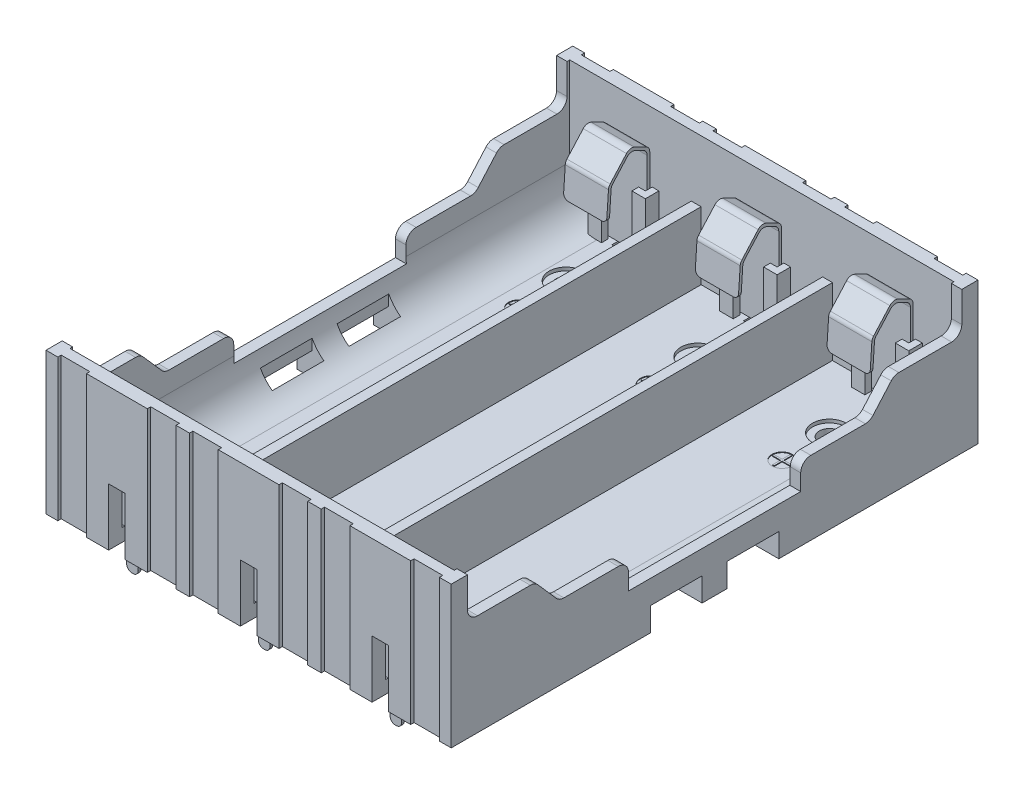
SolidWorks part; units mm, degrees
material "ABS"
ref_plane "Спереди" through (0, 0, 0) normal (0, 0, 1) x (1, 0, 0)
ref_plane "Сверху" through (0, 0, 0) normal (0, 1, 0) x (1, 0, 0)
ref_plane "Справа" through (0, 0, 0) normal (1, 0, 0) x (0, 0, -1)
other "Configuration Table"
sketch "Эскиз1" plane through (0, 0, 0) normal (0, 1, 0) x (1, 0, 0)
  line L1 (-30, 39) -> (30, 39)
  line L2 (-30, 39) -> (-30, -39)
  line L3 (-30, -39) -> (30, -39)
  line L4 (30, 39) -> (30, -39)
  line L5 (-30, 39) -> (30, -39) construction
  line L6 (-30, -39) -> (30, 39) construction
  point P0 (0, 0)
  dimension "D1" = 78
  dimension "D2" = 60
extrude "Основа" add sketch "Эскиз1" along normal blind 21
sketch "Эскиз2" plane through (0, 0, 0) normal (0, 1, 0) x (1, 0, 0)
  line L1 (30, 39) -> (-30, 39) construction
  line L2 (-4.5, 39) -> (-4.5, 38.5)
  line L3 (-4.5, 38.5) -> (-8.75, 38.5)
  line L4 (-8.75, 38.5) -> (-8.75, 39)
  line L5 (-8.75, 39) -> (-10.75, 39)
  line L6 (-10.75, 39) -> (-10.75, 38.5)
  line L7 (-10.75, 38.5) -> (-15, 38.5)
  line L8 (-15, 38.5) -> (-15, 39)
  line L9 (-15, 39) -> (-24, 39)
  line L10 (-24, 39) -> (-24, 38.5)
  line L11 (-24, 38.5) -> (-28.25, 38.5)
  line L12 (-28.25, 38.5) -> (-28.25, 39)
  line L13 (-28.25, 39) -> (-30, 39)
  line L14 (-30, 39) -> (-30, 49.7572)
  line L15 (-30, 49.7572) -> (30, 49.7572)
  line L16 (0, 49.7572) -> (0, 39)
  line L17 (4.5, 39) -> (-4.5, 39)
  line L18 (30, 39) -> (30, 49.7572)
  line L19 (15, 39) -> (24, 39)
  line L20 (24, 39) -> (24, 38.5)
  line L21 (28.25, 38.5) -> (28.25, 39)
  line L22 (24, 38.5) -> (28.25, 38.5)
  line L23 (28.25, 39) -> (30, 39)
  line L24 (15, 38.5) -> (15, 39)
  line L25 (10.75, 38.5) -> (15, 38.5)
  line L26 (10.75, 39) -> (10.75, 38.5)
  line L27 (8.75, 39) -> (10.75, 39)
  line L28 (4.5, 39) -> (4.5, 38.5)
  line L29 (4.5, 38.5) -> (8.75, 38.5)
  line L30 (8.75, 38.5) -> (8.75, 39)
  point P22 (0, 39)
  dimension "D1" = 9
  dimension "D2" = 2
  dimension "D3" = 4.25
  dimension "D4" = 0.5
extrude "Рёбра" cut sketch "Эскиз2" along normal through all contours L29 L30 L27 L26 L25 L24 L19 L20 L22 L21 L23 L18 L15 L16 L17 L28 | L17 L16 L15 L14 L13 L12 L11 L10 L9 L8 L7 L6 L5 L4 L3 L2 region at (-15.004, 0, -44.2695) region at (15.004, 0, -44.2695)
mirror "Зеркальное отражение1" about plane through (0, 0, 0) normal (0, 0, 1) of "Рёбра"
sketch "Эскиз3" plane through (0, 21, 0) normal (0, 1, 0) x (1, 0, 0)
  line L0 (19.45, 0) -> (-19.45, 0) construction
  line L1 (9, 37) -> (-9, 37)
  line L2 (9, 37) -> (9, -37)
  line L3 (9, -37) -> (-9, -37)
  line L4 (-9, 37) -> (-9, -37)
  line L5 (9, 37) -> (-9, -37) construction
  line L6 (9, -37) -> (-9, 37) construction
  line L8 (-28.45, 37) -> (-10.45, 37)
  line L9 (-28.45, 37) -> (-28.45, -37)
  line L10 (-28.45, -37) -> (-10.45, -37)
  line L11 (-10.45, 37) -> (-10.45, -37)
  line L12 (-28.45, 37) -> (-10.45, -37) construction
  line L13 (-28.45, -37) -> (-10.45, 37) construction
  line L15 (28.45, 37) -> (10.45, 37)
  line L16 (28.45, 37) -> (28.45, -37)
  line L17 (28.45, -37) -> (10.45, -37)
  line L18 (10.45, 37) -> (10.45, -37)
  line L19 (28.45, 37) -> (10.45, -37) construction
  line L20 (28.45, -37) -> (10.45, 37) construction
  point P0 (0, 0)
  point P9 (0, 0)
  dimension "D1" = 18
  dimension "D2" = 74
  dimension "D3" = 1.45
extrude "Отсеки" cut sketch "Эскиз3" against normal blind 19.1
fillet "Скругление1" radius 6 2 edges at (28.45, 1.9, 0) (-28.45, 1.9, 0)
sketch "Эскиз4" plane through (0, 0, 0) normal (1, 0, 0) x (0, 0, -1)
  line L0 (37, 21) -> (-37, 21) construction
  line L1 (37, 30.1) -> (-37, 30.1)
  line L2 (37, 30.1) -> (37, 11.9)
  line L3 (37, 11.9) -> (-37, 11.9)
  line L4 (-37, 30.1) -> (-37, 11.9)
  line L5 (37, 30.1) -> (-37, 11.9) construction
  line L6 (37, 11.9) -> (-37, 30.1) construction
  line L7 (-37, 1.9) -> (-37, 21) construction
  line L8 (37, 1.9) -> (-37, 1.9) construction
  point P0 (0, 21)
  dimension "D1" = 10
extrude "Уменьшение внутренних стенок" cut sketch "Эскиз4" against normal blind 15 and the other way blind 15
sketch "Эскиз5" plane through (30, 0, 0) normal (1, 0, 0) x (0, 0, -1)
  line L0 (-39, 21) -> (-36.6, 21)
  line L1 (-39, 21) -> (39, 21) construction
  line L2 (-36.6, 21) -> (-36.6, 15)
  line L3 (-36.6, 15) -> (-26.6, 15)
  line L4 (-26.6, 15) -> (-23, 10.9)
  line L5 (-23, 10.9) -> (-12.75, 10.9)
  line L6 (-12.75, 10.9) -> (-12.75, 7)
  line L7 (-12.75, 7) -> (12.75, 7)
  line L8 (0, 7) -> (0, 0) construction
  line L9 (-36.6, 21) -> (36.6, 21)
  line L10 (12.75, 10.9) -> (12.75, 7)
  line L11 (23, 10.9) -> (12.75, 10.9)
  line L12 (26.6, 15) -> (23, 10.9)
  line L13 (36.6, 15) -> (26.6, 15)
  line L14 (36.6, 21) -> (36.6, 15)
  point P20 (0, 21)
  line M12 (39, 21) -> (-39, 21)
  dimension "D1" = 12.75
  dimension "D2" = 10.25
  dimension "D3" = 2.4
  dimension "D4" = 10
  dimension "D5" = 6
  dimension "D6" = 3.9
  dimension "D7" = 7
extrude "Уменьшение внешних стенок" cut sketch "Эскиз5" against normal blind 15 contours L14 L2 L3 L4 L5 L6 L7 L10 L11 L12 L13 M12 region at (30, 15.4166, 0)
fillet "Скругление2" radius 1.5 8 edges at (29.225, 15, -36.6) (29.225, 15, -26.6) (29.225, 10.9, -23) (29.225, 10.9, -12.75) (29.225, 10.9, 12.75) (29.225, 10.9, 23) (29.225, 15, 26.6) (29.225, 15, 36.6)
mirror "Зеркальное отражение2" about plane through (0, 0, 0) normal (1, 0, 0) of "Скругление2", "Уменьшение внешних стенок"
sketch "Эскиз6" plane through (0, 0, 0) normal (0, 1, 0) x (1, 0, 0)
  line L0 (-4.5, -39) -> (4.5, -39) construction
  line L1 (-1.225, -42.5) -> (1.225, -42.5)
  line L2 (-1.225, -42.5) -> (-1.225, -35.5)
  line L3 (-1.225, -35.5) -> (1.225, -35.5)
  line L4 (1.225, -42.5) -> (1.225, -35.5)
  line L5 (-1.225, -42.5) -> (1.225, -35.5) construction
  line L6 (-1.225, -35.5) -> (1.225, -42.5) construction
  line L7 (-30, 0) -> (30, 0) construction
  line L8 (30, -39) -> (30, 39) construction
  line L9 (-24, -39) -> (-15, -39) construction
  line L10 (-20.725, -42.5) -> (-18.275, -42.5)
  line L11 (-20.725, -42.5) -> (-20.725, -35.5)
  line L12 (-20.725, -35.5) -> (-18.275, -35.5)
  line L13 (-18.275, -42.5) -> (-18.275, -35.5)
  line L14 (-20.725, -42.5) -> (-18.275, -35.5) construction
  line L15 (-20.725, -35.5) -> (-18.275, -42.5) construction
  line L16 (15, -39) -> (24, -39) construction
  line L17 (20.725, -42.5) -> (18.275, -42.5)
  line L18 (20.725, -42.5) -> (20.725, -35.5)
  line L19 (20.725, -35.5) -> (18.275, -35.5)
  line L20 (18.275, -42.5) -> (18.275, -35.5)
  line L21 (20.725, -42.5) -> (18.275, -35.5) construction
  line L22 (20.725, -35.5) -> (18.275, -42.5) construction
  line L23 (20.725, 35.5) -> (18.275, 42.5) construction
  line L24 (20.725, 42.5) -> (18.275, 35.5) construction
  line L25 (-20.725, 35.5) -> (-18.275, 42.5) construction
  line L26 (-20.725, 42.5) -> (-18.275, 35.5) construction
  line L27 (-1.225, 35.5) -> (1.225, 42.5) construction
  line L28 (-1.225, 42.5) -> (1.225, 35.5) construction
  line L29 (18.275, 42.5) -> (18.275, 35.5)
  line L30 (20.725, 35.5) -> (18.275, 35.5)
  line L31 (20.725, 42.5) -> (20.725, 35.5)
  line L32 (20.725, 42.5) -> (18.275, 42.5)
  line L33 (-18.275, 42.5) -> (-18.275, 35.5)
  line L34 (-20.725, 35.5) -> (-18.275, 35.5)
  line L35 (-20.725, 42.5) -> (-20.725, 35.5)
  line L36 (-20.725, 42.5) -> (-18.275, 42.5)
  line L37 (1.225, 42.5) -> (1.225, 35.5)
  line L38 (-1.225, 35.5) -> (1.225, 35.5)
  line L39 (-1.225, 42.5) -> (-1.225, 35.5)
  line L40 (-1.225, 42.5) -> (1.225, 42.5)
  point P0 (0, -39)
  point P7 (-19.5, -39)
  point P13 (0, 0)
  point P21 (19.5, -39)
  point P40 (19.5, 39)
  point P41 (-19.5, 39)
  point P42 (0, 39)
  dimension "D1" = 2.45
  dimension "D2" = 3.5
extrude "Вырезы под контакты" cut sketch "Эскиз6" along normal blind 8.5
sketch "Эскиз7" plane through (0, 0, 0) normal (0, 1, 0) x (1, 0, 0)
  line L0 (0, -35.5) -> (0, 35.5) construction
  line L1 (1.225, -35.5) -> (-1.225, -35.5) construction
  line L2 (-1.225, 35.5) -> (1.225, 35.5) construction
  line L3 (0, 0) -> (-26.025, 0) construction
  line L4 (-26.025, -23.825) -> (-26.025, 23.825) construction
  line L5 (-24, -38.5) -> (-28.25, -38.5) construction
  line L6 (-24.325, -10.8) -> (-27.725, -10.8)
  line L7 (-24.325, -10.8) -> (-24.325, -36.85)
  line L8 (-24.325, -36.85) -> (-27.725, -36.85)
  line L9 (-27.725, -10.8) -> (-27.725, -36.85)
  line L10 (-24.325, -10.8) -> (-27.725, -36.85) construction
  line L11 (-24.325, -36.85) -> (-27.725, -10.8) construction
  line L12 (-24.325, 10.8) -> (-27.725, 10.8)
  line L13 (-24.325, 10.8) -> (-24.325, 36.85)
  line L14 (-24.325, 36.85) -> (-27.725, 36.85)
  line L15 (-27.725, 10.8) -> (-27.725, 36.85)
  line L16 (-24.325, 10.8) -> (-27.725, 36.85) construction
  line L17 (-24.325, 36.85) -> (-27.725, 10.8) construction
  line L18 (-27.725, -1.375) -> (-24.325, -1.375)
  line L19 (-27.725, -1.375) -> (-27.725, 1.375)
  line L20 (-27.725, 1.375) -> (-24.325, 1.375)
  line L21 (-24.325, -1.375) -> (-24.325, 1.375)
  line L22 (-27.725, -1.375) -> (-24.325, 1.375) construction
  line L23 (-27.725, 1.375) -> (-24.325, -1.375) construction
  line L24 (24.325, 36.85) -> (27.725, 36.85)
  line L25 (24.325, 10.8) -> (24.325, 36.85)
  line L26 (27.725, 10.8) -> (27.725, 36.85)
  line L27 (24.325, 10.8) -> (27.725, 10.8)
  line L28 (24.325, -10.8) -> (27.725, -10.8)
  line L29 (24.325, -10.8) -> (24.325, -36.85)
  line L30 (27.725, -10.8) -> (27.725, -36.85)
  line L31 (24.325, -36.85) -> (27.725, -36.85)
  line L32 (27.725, -1.375) -> (27.725, 1.375)
  line L33 (27.725, -1.375) -> (24.325, -1.375)
  line L34 (24.325, -1.375) -> (24.325, 1.375)
  line L35 (27.725, 1.375) -> (24.325, 1.375)
  point P11 (-26.025, 0)
  dimension "D1" = 21.6
  dimension "D2" = 3.4
  dimension "D3" = 2.75
  dimension "D4" = 24.325
  dimension "D5" = 1.65
extrude "Пазы снизу" cut sketch "Эскиз7" along normal blind 1
sketch "Эскиз8" plane through (0, 0, 0) normal (0, 0, 1) x (1, 0, 0)
  line L0 (24.325, 1) -> (27.725, 1)
  line L1 (27.725, 1) -> (27.725, 3.073)
  arc A0 (24.325, 1) -> (27.725, 3.073) centre (22.45, 7.9) ccw
  arc A1 (22.45, 1.9) -> (28.45, 7.9) centre (22.45, 7.9) ccw construction
  arc A2 (22.45, 1.9) -> (28.45, 7.9) centre (22.45, 7.9) ccw construction
extrude "Вырез-Вытянуть9" cut sketch "Эскиз8" against normal up to surface and the other way up to surface up to face at (26.025, 0.5, -1.375) other way up to face at (26.025, 0.5, 1.375)
extrude "Вырез-Вытянуть10" cut sketch "Эскиз8<3>" along direction (0, 0, 1) on the side against the normal up to surface (36.85 mm away) from surface contours A0 L0 L1 region at (26.7298, 1.6233, 0) up to face at (26.025, 0.5, -36.85) starting at face at (26.025, 0.5, -10.8)
sketch "Эскиз8<3>" plane through (0, 0, 0) normal (0, 0, 1) x (1, 0, 0) same geometry as "Эскиз8"
extrude "Вырез-Вытянуть11" cut sketch "Эскиз8<4>" along normal up to surface (36.85 mm away) from surface up to face at (26.025, 0.5, 36.85) starting at face at (26.025, 0.5, 10.8)
sketch "Эскиз8<4>" plane through (0, 0, 0) normal (0, 0, 1) x (1, 0, 0) same geometry as "Эскиз8"
mirror "Зеркальное отражение3" about plane through (0, 0, 0) normal (1, 0, 0) of "Вырез-Вытянуть11", "Вырез-Вытянуть10", "Вырез-Вытянуть9"
sketch "Эскиз9" plane through (0, 0, 0) normal (0, 1, 0) x (1, 0, 0)
  line L0 (-30, 39) -> (-30, -39) construction
  line L1 (-34, -9.5) -> (-26, -9.5)
  line L2 (-34, -9.5) -> (-34, -1.85)
  line L3 (-34, -1.85) -> (-26, -1.85)
  line L4 (-26, -9.5) -> (-26, -1.85)
  line L5 (-34, -9.5) -> (-26, -1.85) construction
  line L6 (-34, -1.85) -> (-26, -9.5) construction
  line L7 (0, 0) -> (-30, 0) construction
  line L8 (-34, 1.85) -> (-26, 1.85)
  line L9 (-34, 1.85) -> (-34, 9.5)
  line L10 (-34, 9.5) -> (-26, 9.5)
  line L11 (-26, 1.85) -> (-26, 9.5)
  line L12 (-34, 1.85) -> (-26, 9.5) construction
  line L13 (-34, 9.5) -> (-26, 1.85) construction
  line L14 (-30, 0) -> (-30, 5.675) construction
  line L15 (-30, 0) -> (-30, -5.675) construction
  line L16 (0, 0) -> (0, -8.7492) construction
  line L17 (30, 0) -> (30, -5.675) construction
  line L18 (30, 0) -> (30, 5.675) construction
  line L19 (34, 9.5) -> (26, 1.85) construction
  line L20 (34, 1.85) -> (26, 9.5) construction
  line L21 (34, -1.85) -> (26, -9.5) construction
  line L22 (34, -9.5) -> (26, -1.85) construction
  line L23 (26, 1.85) -> (26, 9.5)
  line L24 (34, 9.5) -> (26, 9.5)
  line L25 (34, 1.85) -> (34, 9.5)
  line L26 (34, 1.85) -> (26, 1.85)
  line L27 (26, -9.5) -> (26, -1.85)
  line L28 (34, -1.85) -> (26, -1.85)
  line L29 (34, -9.5) -> (34, -1.85)
  line L30 (34, -9.5) -> (26, -9.5)
  point P0 (-30, -5.675)
  point P7 (-30, 5.675)
  point P29 (30, 5.675)
  point P30 (30, -5.675)
  dimension "D1" = 7.65
  dimension "D2" = 4
  dimension "D3" = 3.7
extrude "Пазы сбоку" cut sketch "Эскиз9" along normal blind 3.5
sketch "Эскиз10" plane through (0, 0, 0) normal (0, 1, 0) x (1, 0, 0)
  line L2 (-26, -9.5) -> (-26, -1.85) construction
  line L3 (-26, 1.85) -> (-26, 9.5) construction
  line L4 (0, 0) -> (0, -13.336) construction
  line L5 (27.75, 1.85) -> (26, 1.85)
  line L6 (-26, -9.5) -> (-26, -1.85)
  line L7 (-26, 1.85) -> (-26, 9.5)
  line L8 (-26, -1.85) -> (-27.75, -1.85)
  line L9 (-26, -1.85) -> (-30, -1.85) construction
  line L10 (-27.75, -1.85) -> (-27.75, -9.5)
  line L11 (-30, -9.5) -> (-26, -9.5) construction
  line L12 (-27.75, -9.5) -> (-26, -9.5)
  line L13 (-26, 9.5) -> (-27.75, 9.5)
  line L14 (-26.5292, 9.5) -> (-30, 9.5) construction
  line L15 (-27.75, 9.5) -> (-27.75, 1.85)
  line L16 (-30, 1.85) -> (-26, 1.85) construction
  line L17 (-27.75, 1.85) -> (-26, 1.85)
  line L18 (27.75, 9.5) -> (27.75, 1.85)
  line L19 (26, 9.5) -> (27.75, 9.5)
  line L20 (27.75, -9.5) -> (26, -9.5)
  line L21 (27.75, -1.85) -> (27.75, -9.5)
  line L22 (26, -1.85) -> (27.75, -1.85)
  line L23 (26, 1.85) -> (26, 9.5)
  line L24 (26, -9.5) -> (26, -1.85)
  dimension "D1" = 1.75
extrude "Вырез-Вытянуть15" cut sketch "Эскиз10" along normal through all
sketch "Эскиз11" plane through (0, 0, 0) normal (0, 1, 0) x (1, 0, 0)
  line L0 (-19.5, 35.5) -> (-19.5, 27.5) construction
  line L1 (19.5, -27.5) -> (-19.5, -27.5) construction
  line L2 (19.5, -27.5) -> (19.5, 27.5) construction
  line L3 (19.5, 27.5) -> (-19.5, 27.5) construction
  line L4 (-19.5, -27.5) -> (-19.5, 27.5) construction
  line L5 (19.5, -27.5) -> (-19.5, 27.5) construction
  line L6 (19.5, 27.5) -> (-19.5, -27.5) construction
  line L7 (-18.275, 35.5) -> (-20.725, 35.5) construction
  circle A0 centre (-19.5, 27.5) radius 1.5
  circle A1 centre (0, 27.5) radius 1.5
  circle A2 centre (19.5, 27.5) radius 1.5
  circle A3 centre (19.5, -27.5) radius 1.5
  circle A4 centre (0, -27.5) radius 1.5
  circle A5 centre (-19.5, -27.5) radius 1.5
  point P0 (0, 0)
  dimension "D2" = 3
  dimension "D1" = 55
extrude "Крепежные отверстия" cut sketch "Эскиз11" along normal through all
sketch "Эскиз12" plane through (0, 0, 0) normal (0, 1, 0) x (1, 0, 0)
  circle A0 centre (-19.5, 27.5) radius 1.5 construction
  circle A1 centre (0, 27.5) radius 1.5 construction
  circle A2 centre (19.5, 27.5) radius 1.5 construction
  circle A3 centre (19.5, -27.5) radius 1.5 construction
  circle A4 centre (0, -27.5) radius 1.5 construction
  circle A5 centre (-19.5, -27.5) radius 1.5 construction
  circle A6 centre (-19.5, 27.5) radius 1.5
  circle A7 centre (0, 27.5) radius 1.5
  circle A8 centre (19.5, 27.5) radius 1.5
  circle A9 centre (19.5, -27.5) radius 1.5
  circle A10 centre (0, -27.5) radius 1.5
  circle A11 centre (-19.5, -27.5) radius 1.5
  circle A12 centre (-19.5, 27.5) radius 2.8
  circle A13 centre (0, 27.5) radius 2.8
  circle A14 centre (19.5, 27.5) radius 2.8
  circle A15 centre (19.5, -27.5) radius 2.8
  circle A16 centre (0, -27.5) radius 2.8
  circle A17 centre (-19.5, -27.5) radius 2.8
  dimension "D1" = 1.3
extrude "Юбки отверстий" add sketch "Эскиз12" against normal blind 0.3
sketch "Эскиз13" plane through (0, 1.9, 0) normal (0, 1, 0) x (1, 0, 0)
  circle A0 centre (-19.5, -27.5) radius 1.5 construction
  circle A1 centre (0, -27.5) radius 1.5 construction
  circle A2 centre (19.5, 27.5) radius 1.5 construction
  circle A3 centre (0, 27.5) radius 1.5 construction
  circle A4 centre (-19.5, 27.5) radius 1.5 construction
  circle A5 centre (-19.5, -27.5) radius 1.5
  circle A6 centre (0, -27.5) radius 1.5
  circle A7 centre (19.5, 27.5) radius 1.5
  circle A8 centre (0, 27.5) radius 1.5
  circle A9 centre (-19.5, 27.5) radius 1.5
  circle A10 centre (19.5, -27.5) radius 1.5 construction
  circle A11 centre (19.5, -27.5) radius 1.5
  circle A12 centre (-19.5, -27.5) radius 2.5
  circle A13 centre (0, -27.5) radius 2.5
  circle A14 centre (19.5, 27.5) radius 2.5
  circle A15 centre (0, 27.5) radius 2.5
  circle A16 centre (-19.5, 27.5) radius 2.5
  circle A17 centre (19.5, -27.5) radius 2.5
  dimension "D1" = 1
extrude "Вырез-Вытянуть17" cut sketch "Эскиз13" against normal blind 0.5
sketch "Эскиз14" plane through (0, 1.9, 0) normal (0, 1, 0) x (1, 0, 0)
  line L0 (-19.5, 20.5) -> (-19.5, 27.5) construction
  line L1 (19.5, -20.5) -> (-19.5, -20.5) construction
  line L2 (19.5, -20.5) -> (19.5, 20.5) construction
  line L3 (19.5, 20.5) -> (-19.5, 20.5) construction
  line L4 (-19.5, -20.5) -> (-19.5, 20.5) construction
  line L5 (19.5, -20.5) -> (-19.5, 20.5) construction
  line L6 (19.5, 20.5) -> (-19.5, -20.5) construction
  line L7 (0.125, -19.2) -> (-0.125, -19.2)
  line L8 (-19.375, -19.2) -> (-19.625, -19.2)
  line L9 (-19.375, -19.2) -> (-19.375, -21.8)
  line L10 (-19.375, -21.8) -> (-19.625, -21.8)
  line L11 (-19.625, -19.2) -> (-19.625, -21.8)
  line L12 (-19.375, -19.2) -> (-19.625, -21.8) construction
  line L13 (-19.375, -21.8) -> (-19.625, -19.2) construction
  line L14 (-19.375, 21.8) -> (-19.625, 21.8)
  line L15 (-19.375, 21.8) -> (-19.375, 19.2)
  line L16 (-19.375, 19.2) -> (-19.625, 19.2)
  line L17 (-19.625, 21.8) -> (-19.625, 19.2)
  line L18 (-19.375, 21.8) -> (-19.625, 19.2) construction
  line L19 (-19.375, 19.2) -> (-19.625, 21.8) construction
  line L20 (-18.2, 20.625) -> (-20.8, 20.625)
  line L21 (-18.2, 20.625) -> (-18.2, 20.375)
  line L22 (-18.2, 20.375) -> (-20.8, 20.375)
  line L23 (-20.8, 20.625) -> (-20.8, 20.375)
  line L24 (-18.2, 20.625) -> (-20.8, 20.375) construction
  line L25 (-18.2, 20.375) -> (-20.8, 20.625) construction
  line L26 (0.125, -19.2) -> (0.125, -21.8)
  line L27 (0.125, -21.8) -> (-0.125, -21.8)
  line L28 (-0.125, -19.2) -> (-0.125, -21.8)
  line L29 (0.125, 21.8) -> (-0.125, 21.8)
  line L30 (0.125, 21.8) -> (0.125, 19.2)
  line L31 (0.125, 19.2) -> (-0.125, 19.2)
  line L32 (-0.125, 21.8) -> (-0.125, 19.2)
  line L33 (1.3, 20.625) -> (-1.3, 20.625)
  line L34 (1.3, 20.625) -> (1.3, 20.375)
  line L35 (1.3, 20.375) -> (-1.3, 20.375)
  line L36 (-1.3, 20.625) -> (-1.3, 20.375)
  line L37 (0, -20.5) -> (0, 20.5) construction
  line L38 (0.125, -19.2) -> (-0.125, -21.8) construction
  line L39 (0.125, -21.8) -> (-0.125, -19.2) construction
  line L40 (0.125, 21.8) -> (-0.125, 19.2) construction
  line L41 (0.125, 19.2) -> (-0.125, 21.8) construction
  line L42 (1.3, 20.625) -> (-1.3, 20.375) construction
  line L43 (1.3, 20.375) -> (-1.3, 20.625) construction
  line L44 (19.625, -19.2) -> (19.375, -19.2)
  line L45 (19.625, -19.2) -> (19.625, -21.8)
  line L46 (19.625, -21.8) -> (19.375, -21.8)
  line L47 (19.375, -19.2) -> (19.375, -21.8)
  line L48 (19.625, 21.8) -> (19.375, 21.8)
  line L49 (19.625, 21.8) -> (19.625, 19.2)
  line L50 (19.625, 19.2) -> (19.375, 19.2)
  line L51 (19.375, 21.8) -> (19.375, 19.2)
  line L52 (20.8, 20.625) -> (18.2, 20.625)
  line L53 (20.8, 20.625) -> (20.8, 20.375)
  line L54 (20.8, 20.375) -> (18.2, 20.375)
  line L55 (18.2, 20.625) -> (18.2, 20.375)
  line L56 (19.5, -20.5) -> (19.5, 20.5) construction
  line L57 (19.625, -19.2) -> (19.375, -21.8) construction
  line L58 (19.625, -21.8) -> (19.375, -19.2) construction
  line L59 (19.625, 21.8) -> (19.375, 19.2) construction
  line L60 (19.625, 19.2) -> (19.375, 21.8) construction
  line L61 (20.8, 20.625) -> (18.2, 20.375) construction
  line L62 (20.8, 20.375) -> (18.2, 20.625) construction
  circle A0 centre (-19.5, 20.5) radius 1.5
  circle A1 centre (-19.5, -20.5) radius 1.5
  circle A2 centre (0, 20.5) radius 1.5
  circle A3 centre (0, -20.5) radius 1.5
  circle A4 centre (19.5, 20.5) radius 1.5
  circle A5 centre (19.5, -20.5) radius 1.5
  point P0 (0, 0)
  dimension "D2" = 3
  dimension "D1" = 7
  dimension "D3" = 2.6
  dimension "D4" = 0.25
  dimension "D5" = 3
extrude "Полярность" cut sketch "Эскиз14" against normal blind 0.1 contours A3 L28 L7 L26 L27 | A5 L47 L44 L45 L46 | A1 L11 L8 L9 L10 | A0 L23 L20 L17 L14 L15 L21 L22 L16 | A2 L36 L33 L32 L29 L30 L34 L35 L31 | A4 L55 L52 L51 L48 L49 L53 L54 L50 region at (-20.9576, 1.9, -20.5) region at (-20.9576, 1.9, 20.5) region at (-1.4576, 1.9, -20.5) region at (-1.4576, 1.9, 20.5) region at (18.0424, 1.9, -20.5) region at (18.0424, 1.9, 20.5)
sketch "Эскиз15" plane through (0, 1.9, 0) normal (0, 1, 0) x (1, 0, 0)
  line L0 (-19.5, 35.5) -> (-19.5, 35) construction
  line L1 (-18.275, 35.5) -> (-20.725, 35.5) construction
  line L2 (-21.75, 35) -> (-17.25, 35) construction
  line L3 (-21.75, 35) -> (-23.75, 35)
  line L4 (-23.75, 35) -> (-23.75, 37)
  line L5 (28.45, 37) -> (-28.45, 37) construction
  line L6 (-23.75, 37) -> (-22.75, 37)
  line L7 (-22.75, 37) -> (-22.75, 36)
  line L8 (-22.75, 36) -> (-21.75, 36)
  line L9 (-21.75, 36) -> (-21.75, 35)
  line L10 (-17.25, 35) -> (-17.25, 36)
  line L11 (-17.25, 36) -> (-16.25, 36)
  line L12 (-16.25, 36) -> (-16.25, 37)
  line L13 (-16.25, 37) -> (-15.25, 37)
  line L14 (-15.25, 37) -> (-15.25, 35)
  line L15 (-15.25, 35) -> (-17.25, 35)
  line L16 (-2.25, 35) -> (-4.25, 35)
  line L17 (-4.25, 35) -> (-4.25, 37)
  line L18 (-4.25, 37) -> (-3.25, 37)
  line L19 (-3.25, 37) -> (-3.25, 36)
  line L20 (-3.25, 36) -> (-2.25, 36)
  line L21 (-2.25, 36) -> (-2.25, 35)
  line L22 (2.25, 35) -> (2.25, 36)
  line L23 (2.25, 36) -> (3.25, 36)
  line L24 (3.25, 36) -> (3.25, 37)
  line L25 (3.25, 37) -> (4.25, 37)
  line L26 (4.25, 37) -> (4.25, 35)
  line L27 (4.25, 35) -> (2.25, 35)
  line L28 (0, 35.5) -> (0, 35) construction
  line L29 (-2.25, 35) -> (2.25, 35) construction
  line L30 (17.25, 35) -> (15.25, 35)
  line L31 (15.25, 35) -> (15.25, 37)
  line L32 (15.25, 37) -> (16.25, 37)
  line L33 (16.25, 37) -> (16.25, 36)
  line L34 (16.25, 36) -> (17.25, 36)
  line L35 (17.25, 36) -> (17.25, 35)
  line L36 (21.75, 35) -> (21.75, 36)
  line L37 (21.75, 36) -> (22.75, 36)
  line L38 (22.75, 36) -> (22.75, 37)
  line L39 (22.75, 37) -> (23.75, 37)
  line L40 (23.75, 37) -> (23.75, 35)
  line L41 (23.75, 35) -> (21.75, 35)
  line L42 (19.5, 35.5) -> (19.5, 35) construction
  line L43 (17.25, 35) -> (21.75, 35) construction
  line L44 (30, 0) -> (-30, 0) construction
  line L45 (-30, -12.75) -> (-30, 12.75) construction
  line L46 (17.25, -35) -> (21.75, -35) construction
  line L47 (19.5, -35.5) -> (19.5, -35) construction
  line L48 (-2.25, -35) -> (2.25, -35) construction
  line L49 (0, -35.5) -> (0, -35) construction
  line L50 (-21.75, -35) -> (-17.25, -35) construction
  line L51 (-19.5, -35.5) -> (-19.5, -35) construction
  line L52 (23.75, -35) -> (21.75, -35)
  line L53 (23.75, -37) -> (23.75, -35)
  line L54 (22.75, -37) -> (23.75, -37)
  line L55 (22.75, -36) -> (22.75, -37)
  line L56 (21.75, -36) -> (22.75, -36)
  line L57 (21.75, -35) -> (21.75, -36)
  line L58 (17.25, -36) -> (17.25, -35)
  line L59 (16.25, -36) -> (17.25, -36)
  line L60 (16.25, -37) -> (16.25, -36)
  line L61 (15.25, -37) -> (16.25, -37)
  line L62 (15.25, -35) -> (15.25, -37)
  line L63 (17.25, -35) -> (15.25, -35)
  line L64 (4.25, -35) -> (2.25, -35)
  line L65 (4.25, -37) -> (4.25, -35)
  line L66 (3.25, -37) -> (4.25, -37)
  line L67 (3.25, -36) -> (3.25, -37)
  line L68 (2.25, -36) -> (3.25, -36)
  line L69 (2.25, -35) -> (2.25, -36)
  line L70 (-2.25, -36) -> (-2.25, -35)
  line L71 (-3.25, -36) -> (-2.25, -36)
  line L72 (-3.25, -37) -> (-3.25, -36)
  line L73 (-4.25, -37) -> (-3.25, -37)
  line L74 (-4.25, -35) -> (-4.25, -37)
  line L75 (-2.25, -35) -> (-4.25, -35)
  line L76 (-15.25, -35) -> (-17.25, -35)
  line L77 (-15.25, -37) -> (-15.25, -35)
  line L78 (-16.25, -37) -> (-15.25, -37)
  line L79 (-16.25, -36) -> (-16.25, -37)
  line L80 (-17.25, -36) -> (-16.25, -36)
  line L81 (-17.25, -35) -> (-17.25, -36)
  line L82 (-21.75, -36) -> (-21.75, -35)
  line L83 (-22.75, -36) -> (-21.75, -36)
  line L84 (-22.75, -37) -> (-22.75, -36)
  line L85 (-23.75, -37) -> (-22.75, -37)
  line L86 (-23.75, -35) -> (-23.75, -37)
  line L87 (-21.75, -35) -> (-23.75, -35)
  point P7 (-19.5, 35)
  point P24 (0, 35)
  point P39 (19.5, 35)
  point P55 (0, 0)
  point P98 (19.5, -35)
  point P99 (0, -35)
  point P100 (-19.5, -35)
  dimension "D1" = 2
  dimension "D2" = 1
  dimension "D3" = 8.5
  dimension "D4" = 2
  dimension "D5" = 3
extrude "Пазы для контактов" add sketch "Эскиз15" along normal blind 8.9
ref_plane "Для эскиза контактов" through (-19.5, 0, 0) normal (-1, 0, 0) x (0, 0, 1)
sketch "Эскиз16" plane through (-19.5, 0, 0) normal (-1, 0, 0) x (0, 0, 1)
  line L0 (-37, 6.35) -> (-36, 6.35) construction
  line L1 (-37, 10.8) -> (-37, 1.9) construction
  line L2 (-36, 10.8) -> (-36, 1.9) construction
  line L3 (-36.5, 17.26) -> (-36.5, 15.9523) construction
  line L4 (-36.5, 15.9523) -> (-33.8, 17.26)
  line L5 (-33.8, 17.26) -> (-30.8, 13.9059)
  line L6 (-30.8, 13.9059) -> (-30.5, 9.4159)
  line L7 (-36.5, 17.26) -> (-33.8, 17.26) construction
  line L8 (-36.5, 15.9523) -> (-36.5, 2)
  line L9 (-35.5, 0) -> (-39, 0) construction
  line L10 (-36.5, 2) -> (-36.5, -3.54) construction
  line L11 (-37, 1.9) -> (-35.5, 1.9) construction
  point P8 (-36.4926, -3.4204)
  point P12 (-36.4066, 16.649)
  point P14 (-36.6083, 15.954)
  point P17 (-36.5, 6.35)
  point P20 (-36.214, 3.8899)
  dimension "D1" = 20.8
  dimension "D2" = 3
  dimension "D3" = 4.5
  dimension "D4" = 6
  dimension "D5" = 5.7
  dimension "D6" = 2.7
  dimension "D7" = 3.54
  dimension "D8" = 0.1
extrude "Контакт" add sketch "Эскиз16" along normal mid plane 6.4 thin thin type mid plane wall 0.4
sketch "Эскиз17" plane through (0, 2, 0) normal (0, -1, 0) x (1, 0, 0)
  line L0 (-19.5, -36.7) -> (-19.5, -36.3) construction
  line L1 (-22.7, -36.7) -> (-16.3, -36.7) construction
  line L2 (-22.7, -36.3) -> (-16.3, -36.3) construction
  line L4 (-18.65, -36.3) -> (-20.35, -36.3)
  line L5 (-18.65, -36.3) -> (-18.65, -36.7)
  line L6 (-18.65, -36.7) -> (-20.35, -36.7)
  line L7 (-20.35, -36.3) -> (-20.35, -36.7)
  line L8 (-18.65, -36.3) -> (-20.35, -36.7) construction
  line L9 (-18.65, -36.7) -> (-20.35, -36.3) construction
  point P6 (-19.5, -36.5)
  dimension "D1" = 1.7
extrude "Штырёк для пайки" add sketch "Эскиз17" along normal blind 5.5
fillet "Скругление3" radius 1 6 edges at (-19.5, 13.8239, -30.995) (-19.5, 13.9879, -30.605) (-19.5, 17.0143, -33.8485) (-19.5, 17.5057, -33.7515) (-19.5, 15.827, -36.3) (-19.5, 16.0777, -36.7)
fillet "Скругление4" radius 0.75 6 edges at (-16.3, 2, -36.5) (-18.65, -3.5, -36.5) (-20.35, -3.5, -36.5) (-22.7, 2, -36.5) (-16.3, 9.4159, -30.5) (-22.7, 9.4159, -30.5)
pattern_linear "Линейный массив1" count 3 spacing 19.5 along (1, 0, 0) of bodies 125
mirror "Зеркальное отражение4" about plane through (0, 0, 0) normal (0, 0, 1) of bodies 127 126 125
equation "\"D1@Эскиз5\"=25.5/2"
equation "\"D4@Эскиз7\"=48.65/2"
